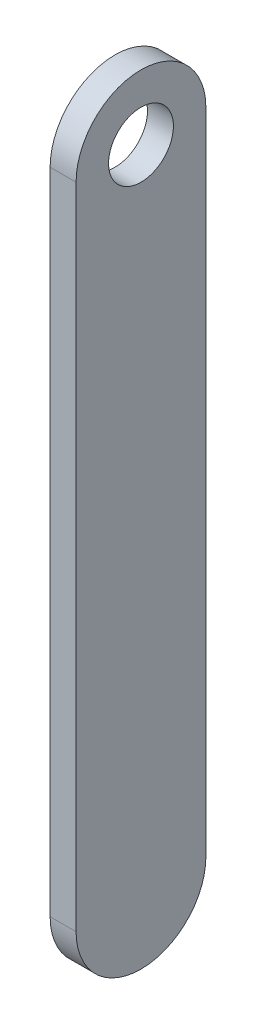
SolidWorks part; units mm, degrees
ref_plane "Front Plane" through (0, 0, 0) normal (0, 0, 1) x (1, 0, 0)
ref_plane "Top Plane" through (0, 0, 0) normal (0, 1, 0) x (1, 0, 0)
ref_plane "Right Plane" through (0, 0, 0) normal (1, 0, 0) x (0, 0, -1)
sketch "Sketch2" plane through (0, 0, 0) normal (1, 0, 0) x (0, 0, -1)
  line L0 (-36.0645, 0) -> (36.0645, 0) construction
  line L1 (0, 90.2048) -> (0, -90.2048) construction
  line L2 (-20, 0) -> (-20, -200)
  line L3 (20, 0) -> (20, -200)
  line L4 (-20, -200) -> (20, -200) construction
  line L5 (0, -163.4104) -> (0, -236.5896) construction
  circle A0 centre (0, 0) radius 20
  circle A2 centre (0, -200) radius 20
  circle A3 centre (0, 0) radius 10
  point P3 (0, 0)
  point P6 (0, 0)
  point P13 (0, -200)
  dimension "D1" = 40
  dimension "D3" = 20
  dimension "D2" = 200
extrude "Boss-Extrude1" add sketch "Sketch2" along normal blind 4 and the other way blind 4 contours A2 L3 A0 L2 | A0 A3 | A2 region at (0, -100, 0) region at (0, 19.4343, 0) region at (0, -200, 0)
